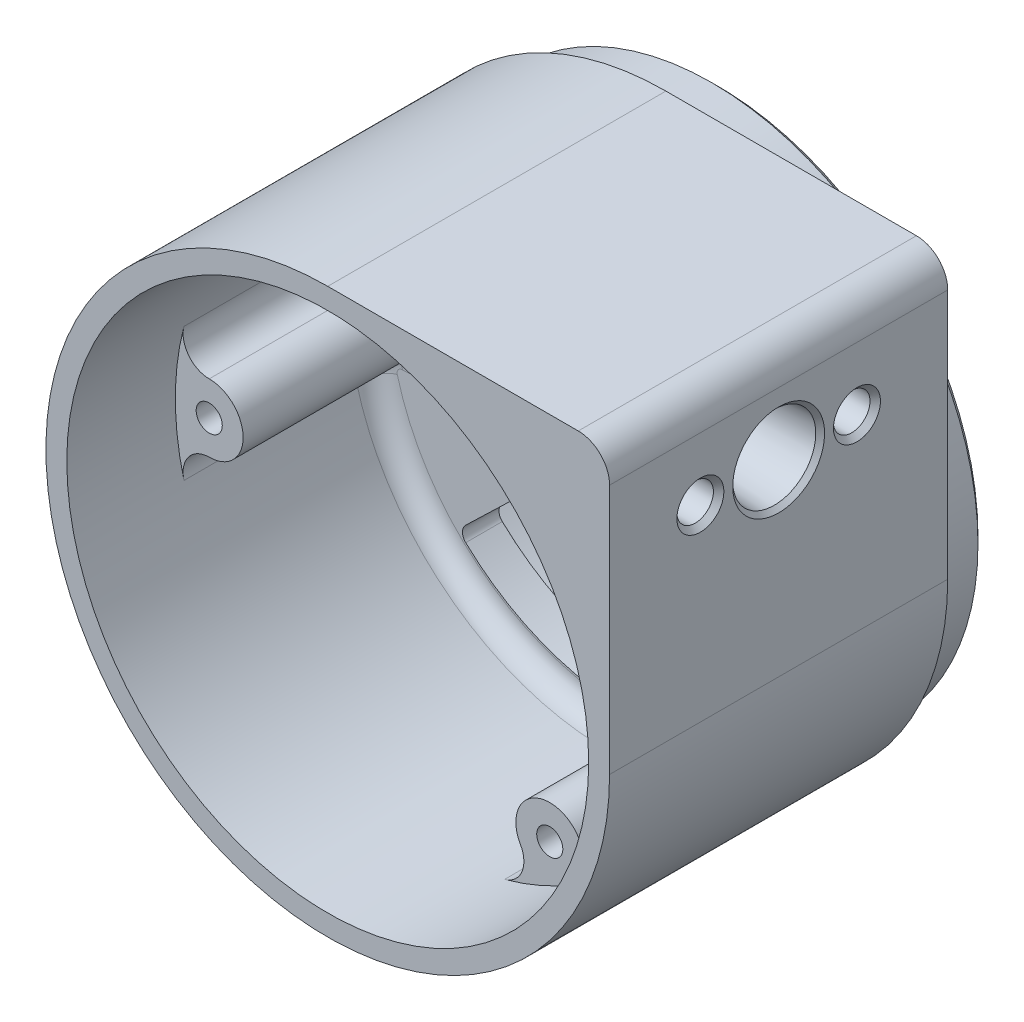
SolidWorks part; units mm, degrees
ref_plane "Front Plane" through (0, 0, 0) normal (0, 0, 1) x (1, 0, 0)
ref_plane "Top Plane" through (0, 0, 0) normal (0, 1, 0) x (1, 0, 0)
ref_plane "Right Plane" through (0, 0, 0) normal (1, 0, 0) x (0, 0, -1)
sketch "Sketch1" plane through (0, 0, 0) normal (0, 0, 1) x (1, 0, 0)
  line L0 (-12.5, 0) -> (0, 0) construction
  line L1 (0, 0) -> (6.25, 10.8253) construction
  line L2 (6.25, -10.8253) -> (0, 0) construction
  circle A0 centre (0, 0) radius 27
  circle A1 centre (0, 0) radius 12.5 construction
  circle A2 centre (0, 0) radius 7.75
  circle A3 centre (0, 0) radius 3 construction
  circle A4 centre (6.25, 10.8253) radius 2.25
  circle A5 centre (-12.5, 0) radius 2.25
  circle A6 centre (6.25, -10.8253) radius 2.25
  dimension "D1" = 54
  dimension "D2" = 6
  dimension "D3" = 15.5
  dimension "D4" = 25
  dimension "D7" = 4.5
  dimension "D5" = 120
  dimension "D6" = 120
extrude "Boss-Extrude1" add sketch "Sketch1" along normal blind 28
sketch "Sketch2" plane through (0, 0, 28) normal (0, 0, 1) x (1, 0, 0)
  circle A0 centre (6.25, 10.8253) radius 3.75
  circle A1 centre (6.25, -10.8253) radius 3.75
  circle A2 centre (-12.5, 0) radius 3.75
  dimension "D1" = 7.5
extrude "Cut-Extrude1" cut sketch "Sketch2" against normal offset from surface (23.5 mm away) 4.5 up to face at (27, 0, 0)
sketch "Sketch3" plane through (0, 0, 28) normal (0, 0, 1) x (1, 0, 0)
  line L0 (13.9654, 0) -> (0, 13.9654) construction
  line L1 (0, -17.6777) -> (17.6777, 0) construction
  line L2 (0, -17.6777) -> (-17.6777, 0) construction
  line L3 (-17.6777, 0) -> (0, 17.6777) construction
  line L4 (17.6777, 0) -> (0, 17.6777) construction
  line L5 (0, -17.6777) -> (0, 17.6777) construction
  line L6 (-17.6777, 0) -> (17.6777, 0) construction
  line L7 (0, 13.9654) -> (-13.9654, 0) construction
  line L8 (-13.9654, 0) -> (0, -13.9654) construction
  line L9 (0, -13.9654) -> (13.9654, 0) construction
  line L10 (-17.9605, 0) -> (0, 17.9605)
  line L11 (17.9605, 0) -> (0, 17.9605)
  line L12 (0, -17.9605) -> (17.9605, 0)
  line L13 (0, -17.9605) -> (-17.9605, 0)
  circle A0 centre (13.9654, 0) radius 1.625 construction
  circle A1 centre (0, -13.9654) radius 1.625 construction
  circle A2 centre (-13.9654, 0) radius 1.625 construction
  circle A3 centre (0, 13.9654) radius 1.625 construction
  point P0 (0, 0)
  dimension "D2" = 3.25
  dimension "D3" = 1
  dimension "D1" = 25
  dimension "D4" = 0.2
sketch "Sketch5" plane through (0, 0, 28) normal (0, 0, 1) x (1, 0, 0)
  line L0 (0, 27) -> (24, 27)
  line L3 (27, 0) -> (27, 24)
  circle A0 centre (0, 0) radius 27 construction
  arc A1 (0, 27) -> (27, 0) centre (0, 0) cw
  arc A3 (24, 27) -> (27, 24) centre (24, 24) cw
extrude "Boss-Extrude2" add sketch "Sketch5" against normal up to surface (28 mm away) up to face at (27, 0, 0)
sketch "Sketch8" plane through (0, 0, 0) normal (0, 0, -1) x (-1, 0, 0)
  circle A0 centre (0, 0) radius 8.625
  dimension "D1" = 17.25
extrude "Cut-Extrude5" cut sketch "Sketch8" against normal blind 2
chamfer "Chamfer2" distance 1 angle 72 1 edges at (-7.75, 0, 2) first distance on face at (-7.75, 0, 2)
sketch "Sketch9" plane through (0, 0, 28) normal (0, 0, 1) x (1, 0, 0)
  circle A0 centre (0, 0) radius 25
  dimension "D1" = 50
extrude "Cut-Extrude6" cut sketch "Sketch9" against normal offset from surface (24.5 mm away) 3.5 up to face at (-8.625, 0, 0)
sketch "Sketch10" plane through (0, 0, 3.5) normal (0, 0, 1) x (1, 0, 0)
  line L0 (0, 0) -> (11.1505, 11.1233) construction
  line L1 (0, 0) -> (4.0578, -15.2183) construction
  line L2 (0, 0) -> (-15.2083, 4.095) construction
  line L3 (0, 0) -> (-2.716, 15.5141) construction
  line L4 (0, 0) -> (-12.0776, -10.1091) construction
  line L5 (0, 0) -> (13.8224, -5.0501) construction
  line L6 (-14.21, 3.8262) -> (-12.2736, 3.3048)
  line L7 (-2.1919, 12.5203) -> (-2.5377, 14.4956)
  line L8 (10.4185, 10.3931) -> (8.9988, 8.9768)
  line L9 (11.9388, -4.3619) -> (14.7936, -5.4049)
  line L10 (3.7914, -14.2193) -> (3.2748, -12.2816)
  line L11 (-9.747, -8.1584) -> (-11.2847, -9.4455)
  circle A0 centre (0, 0) radius 15.75 construction
  circle A1 centre (0, 0) radius 11.75 construction
  circle A2 centre (6.25, 10.8253) radius 2.25 construction
  arc A3 (-1.6579, 15.6625) -> (10.3708, 11.8537) centre (0, 0) cw
  arc A4 (14.3931, -6.3954) -> (5.0802, -14.9082) centre (0, 0) cw
  arc A5 (-15.451, 3.0545) -> (-12.7351, -9.2671) centre (0, 0) ccw
  arc A6 (-11.0713, 3.9355) -> (-2.9277, 11.3794) centre (0, 0) cw
  arc A7 (8.9439, 7.6203) -> (11.3187, -3.1542) centre (0, 0) cw
  arc A8 (2.1275, -11.5558) -> (-8.391, -8.2252) centre (0, 0) cw
  arc A9 (-8.391, -8.2252) -> (-9.747, -8.1584) centre (-9.1051, -8.9252) ccw
  arc A10 (2.1275, -11.5558) -> (3.2748, -12.2816) centre (2.3085, -12.5393) cw
  arc A11 (3.7914, -14.2193) -> (5.0802, -14.9082) centre (4.7577, -13.9616) ccw
  arc A12 (11.3187, -3.1542) -> (11.9388, -4.3619) centre (12.282, -3.4227) ccw
  arc A13 (14.3931, -6.3954) -> (13.8224, -5.0501) centre (13.4792, -5.9894) ccw
  arc A14 (8.9439, 7.6203) -> (8.9988, 8.9768) centre (9.7051, 8.2689) cw
  arc A15 (10.4185, 10.3931) -> (10.3708, 11.8537) centre (9.7123, 11.1011) ccw
  arc A16 (-2.5377, 14.4956) -> (-1.6579, 15.6625) centre (-1.5527, 14.6681) cw
  arc A17 (-2.9277, 11.3794) -> (-2.1919, 12.5203) centre (-3.1769, 12.3479) ccw
  arc A18 (-11.0713, 3.9355) -> (-12.2736, 3.3048) centre (-12.0136, 4.2704) cw
  arc A19 (-14.21, 3.8262) -> (-15.451, 3.0545) centre (-14.47, 2.8606) ccw
  arc A20 (-12.7351, -9.2671) -> (-11.2847, -9.4455) centre (-11.9266, -8.6787) ccw
  point P23 (-9.0103, -7.5417)
  point P26 (3.0272, -11.3533)
  point P31 (11.0365, -4.0322)
  point P37 (8.3187, 8.2983)
  point P46 (-2.0262, 11.574)
  point P49 (-11.3459, 3.055)
  dimension "D1" = 23.5
  dimension "D2" = 31.5
  dimension "D6" = 55
  dimension "D9" = 1
  dimension "D3" = 120
  dimension "D4" = 120
  dimension "D5" = 1
  dimension "D7" = 55
  dimension "D8" = 55
sketch "Sketch11" plane through (0, 0, 3.5) normal (0, 0, 1) x (1, 0, 0)
  line L0 (-3.3134, 13.3589) -> (-5.2425, 21.1366)
  line L1 (-13.0084, 4.4969) -> (-20.5819, 7.1151)
  line L2 (10.3986, 9.0171) -> (16.4528, 14.2669)
  line L3 (-14.21, 3.8262) -> (-12.2736, 3.3048) construction
  line L4 (-2.1919, 12.5203) -> (-2.5377, 14.4956) construction
  line L5 (13.2259, -3.81) -> (20.9261, -6.0282)
  line L6 (2.6097, -13.514) -> (4.1291, -21.382)
  line L7 (-9.9125, -9.549) -> (-15.6836, -15.1084)
  line L8 (0, 0) -> (-3.9736, 12.1676) construction
  line L9 (0, 0) -> (12.5242, -2.6426) construction
  arc A0 (-3.9736, 12.1676) -> (-11.7627, 5.0477) centre (0, 0) ccw
  circle A1 centre (0, 0) radius 25 construction
  arc A2 (-21.1843, 8.4299) -> (-20.5819, 7.1151) centre (-20.2552, 8.0602) ccw
  arc A3 (-6.4981, 21.8544) -> (-21.1843, 8.4299) centre (0, 0) ccw
  arc A4 (-11.7627, 5.0477) -> (-13.0084, 4.4969) centre (-12.6816, 5.4421) cw
  arc A5 (-3.9736, 12.1676) -> (-3.3134, 13.3589) centre (-4.284, 13.1182) ccw
  arc A6 (-5.2425, 21.1366) -> (-6.4981, 21.8544) centre (-6.2131, 20.8959) ccw
  arc A7 (10.2528, 7.6629) -> (10.3986, 9.0171) centre (11.0538, 8.2616) cw
  arc A8 (17.8927, 14.1312) -> (16.4528, 14.2669) centre (17.1079, 13.5114) ccw
  arc A9 (22.1755, -5.2997) -> (17.8927, 14.1312) centre (0, 0) ccw
  arc A10 (20.9261, -6.0282) -> (22.1755, -5.2997) centre (21.2029, -5.0672) ccw
  arc A11 (12.5242, -2.6426) -> (13.2259, -3.81) centre (13.5027, -2.849) ccw
  arc A12 (12.5242, -2.6426) -> (10.2528, 7.6629) centre (0, 0) ccw
  arc A13 (1.5099, -12.7106) -> (2.6097, -13.514) centre (1.6279, -13.7037) cw
  arc A14 (3.2916, -22.5611) -> (4.1291, -21.382) centre (3.1473, -21.5716) ccw
  arc A15 (-15.6774, -16.5547) -> (3.2916, -22.5611) centre (0, 0) ccw
  arc A16 (-15.6836, -15.1084) -> (-15.6774, -16.5547) centre (-14.9898, -15.8286) ccw
  arc A17 (-8.5507, -9.525) -> (-9.9125, -9.549) centre (-9.2187, -10.2692) ccw
  arc A18 (-8.5507, -9.525) -> (1.5099, -12.7106) centre (0, 0) ccw
  dimension "D3" = 10
  dimension "D4" = 2.2
  dimension "D5" = 1
  dimension "D1" = 4
  dimension "D2" = 4
  dimension "D6" = 120
extrude "Cut-Extrude7" cut sketch "Sketch11" against normal through all
sketch "Sketch13" plane through (0, 0, 0) normal (0, 0, -1) x (-1, 0, 0)
  circle A0 centre (0, 0) radius 24.2
  arc A1 (-27, 0) -> (0, 27) centre (0, 0) ccw construction
  circle A2 centre (0, 0) radius 25.5
  dimension "D1" = 2.8
  dimension "D2" = 1.5
extrude "Boss-Extrude3" add sketch "Sketch13" along normal blind 5
fillet "Fillet2" radius 1 1 edges at (-24.2, 0, 0)
chamfer "Chamfer3" distance 0.6 angle 45 1 edges at (-25.5, 0, -5)
sketch "Sketch14" plane through (0, 0, 3.5) normal (0, 0, 1) x (1, 0, 0)
  line L0 (0, 0) -> (-25, 0) construction
  line L1 (0, 0) -> (12.5, 21.6506) construction
  line L2 (0, 0) -> (12.5, -21.6506) construction
  circle A0 centre (0, 0) radius 25 construction
  circle A1 centre (0, 0) radius 25 construction
  circle A2 centre (6.25, -10.8253) radius 2.25 construction
  circle A3 centre (6.25, -10.8253) radius 2.25 construction
  circle A4 centre (6.25, 10.8253) radius 2.25 construction
  circle A5 centre (-12.5, 0) radius 2.25 construction
  circle A6 centre (6.25, 10.8253) radius 2.25 construction
  circle A7 centre (-12.5, 0) radius 2.25 construction
  circle A8 centre (-21.75, 0) radius 3.25 construction
  arc A9 (-21.75, 3.25) -> (-24.169, 6.392) centre (-21.75, 5.7522) cw
  arc A10 (-21.75, -3.25) -> (-24.169, -6.392) centre (-21.75, -5.7522) ccw
  arc A11 (-21.75, 3.25) -> (-21.75, -3.25) centre (-21.75, 0) cw
  arc A12 (-24.169, 6.392) -> (-24.169, -6.392) centre (0, 0) ccw
  arc A13 (13.6896, 17.2111) -> (17.6201, 17.735) centre (15.8566, 15.9599) cw
  arc A14 (8.0604, 20.4611) -> (6.5489, 24.127) centre (5.8934, 21.7122) ccw
  arc A15 (13.6896, 17.2111) -> (8.0604, 20.4611) centre (10.875, 18.8361) cw
  arc A16 (17.6201, 17.735) -> (6.5489, 24.127) centre (0, 0) ccw
  circle A17 centre (10.875, 18.8361) radius 3.25 construction
  arc A18 (8.0604, -20.4611) -> (6.5489, -24.127) centre (5.8934, -21.7122) cw
  arc A19 (13.6896, -17.2111) -> (17.6201, -17.735) centre (15.8566, -15.9599) ccw
  arc A20 (8.0604, -20.4611) -> (13.6896, -17.2111) centre (10.875, -18.8361) cw
  arc A21 (6.5489, -24.127) -> (17.6201, -17.735) centre (0, 0) ccw
  circle A22 centre (10.875, -18.8361) radius 3.25 construction
  circle A23 centre (-21.75, 0) radius 1.25
  circle A24 centre (10.875, -18.8361) radius 1.25
  circle A25 centre (10.875, 18.8361) radius 1.25
  point P49 (0, 0)
  dimension "D1" = 6.5
  dimension "D3" = 2.5
  dimension "D2" = 3
extrude "Boss-Extrude4" add sketch "Sketch14" along normal offset from surface (18.5 mm away) 6 up to face at (25, 0, 28)
fillet "Fillet4" radius 2 12 edges at (8.2067, 22.666, 3.5) (-12.5, 21.6506, 3.5) (-23.7327, 4.2257, 3.5) (-18.5, 0, 3.5) (-23.7327, -4.2257, 3.5) (-12.5, -21.6506, 3.5) (8.2067, -22.666, 3.5) (9.25, -16.0215, 3.5) (15.5259, -18.4402, 3.5) (25, 0, 3.5) (15.5259, 18.4402, 3.5) (9.25, 16.0215, 3.5)
sketch "Sketch16" plane through (0, 0, 28) normal (0, 0, 1) x (1, 0, 0)
  line L2 (27, 0) -> (27, 24)
  line L3 (24, 27) -> (0, 27)
  line L4 (27, 0) -> (27, 24)
  line L5 (24, 27) -> (0, 27)
  circle A0 centre (0, 0) radius 25 construction
  circle A1 centre (0, 0) radius 25
  arc A2 (0, 27) -> (27, 0) centre (0, 0) ccw
  arc A3 (27, 24) -> (24, 27) centre (24, 24) ccw
  arc A4 (0, 27) -> (27, 0) centre (0, 0) ccw
  arc A5 (27, 24) -> (24, 27) centre (24, 24) ccw
  dimension "D1" = 0
extrude "Boss-Extrude5" add sketch "Sketch16" along normal up to surface (4.395 mm away)
sketch "Sketch6" plane through (27, 0, 0) normal (1, 0, 0) x (0, 0, -1)
  line L0 (-16.1975, 27) -> (-16.1975, -27) construction
  line L3 (0, 27) -> (-32.395, 27) construction
  line L5 (-32.395, -27) -> (0, -27) construction
  circle A0 centre (-16.1975, 18) radius 4
  dimension "D1" = 8
  dimension "D2" = 9
extrude "Cut-Extrude4" cut sketch "Sketch6" against normal blind 6 draft 3
fillet "Fillet3" radius 1 1 edges at (25.5, 0, 0)
sketch "Sketch17" plane through (27, 0, 0) normal (1, 0, 0) x (0, 0, -1)
  line L0 (-32.395, 18) -> (0, 18) construction
  line L1 (-32.395, 0) -> (-32.395, 24) construction
  line L2 (0, 24) -> (0, 0) construction
  line L3 (-23.6975, 18) -> (-8.6975, 18) construction
  circle A2 centre (-16.1975, 18) radius 4 construction
  circle A3 centre (-16.1975, 18) radius 4 construction
  circle A4 centre (-23.6975, 18) radius 1.75
  circle A5 centre (-8.6975, 18) radius 1.75
  point P13 (-16.1975, 18)
  dimension "D1" = 3.5
  dimension "D2" = 15
extrude "Cut-Extrude8" cut sketch "Sketch17" against normal blind 5
chamfer "Chamfer4" distance 1 angle 45 2 edges at (22, 19.75, 8.6975) (22, 19.75, 23.6975)
chamfer "Chamfer5" distance 0.5 angle 45 2 edges at (27, 19.75, 23.6975) (27, 19.75, 8.6975)
chamfer "Chamfer6" distance 0.4 angle 45 1 edges at (27, 22, 16.1975) first distance on face at (27, 20.25, 23.6975)
